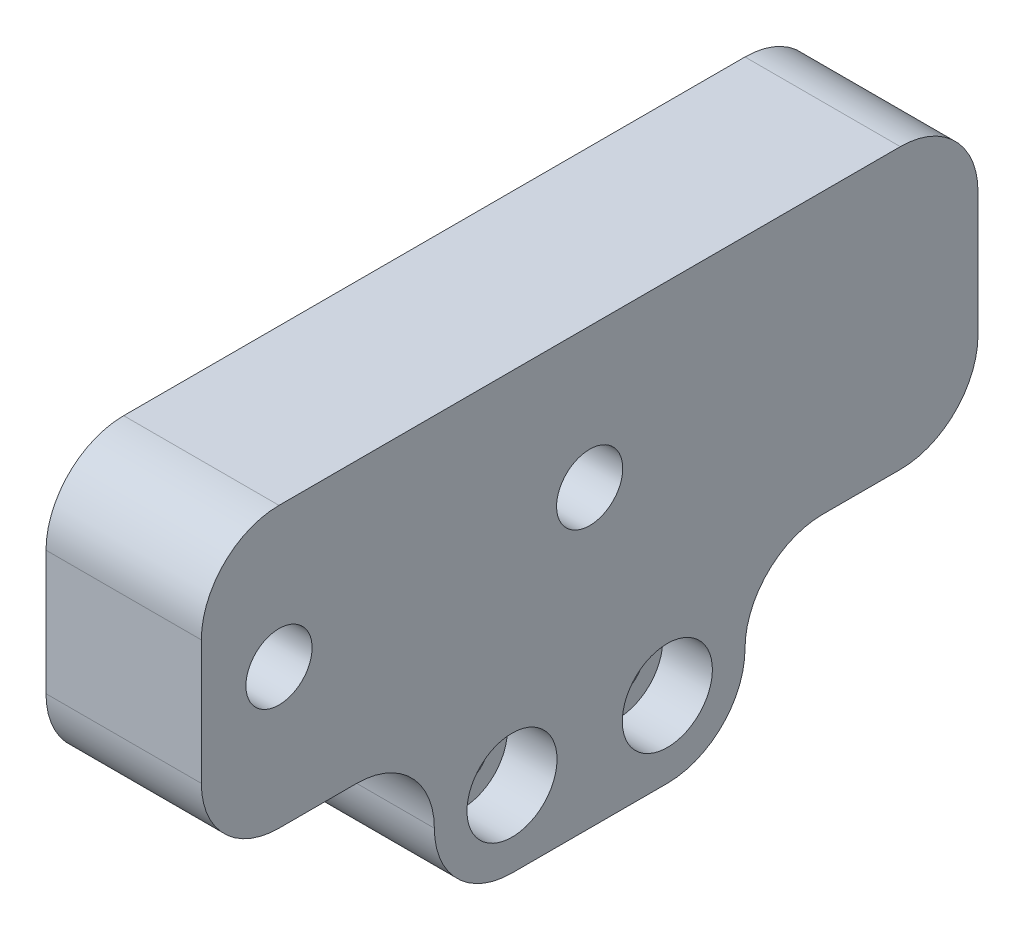
SolidWorks part; units mm, degrees
ref_plane "Front Plane" through (0, 0, 0) normal (0, 0, 1) x (1, 0, 0)
ref_plane "Top Plane" through (0, 0, 0) normal (0, 1, 0) x (1, 0, 0)
ref_plane "Right Plane" through (0, 0, 0) normal (1, 0, 0) x (0, 0, -1)
sketch "Profile" plane through (0, 0, 0) normal (0, 0, 1) x (1, 0, 0)
  line L1 (-6.35, 22.86) -> (6.35, 22.86)
  line L2 (-6.35, 22.86) -> (-6.35, 0)
  line L3 (-6.35, 0) -> (6.35, 0)
  line L4 (6.35, 22.86) -> (6.35, 0)
  line L5 (0, 0) -> (6.35, 0)
  line L6 (0, 0) -> (0, -12.7)
  line L7 (0, -12.7) -> (6.35, -12.7)
  line L8 (6.35, 0) -> (6.35, -12.7)
  dimension "D1" = 22.86
  dimension "D2" = 12.7
  dimension "D3" = 6.35
  dimension "D4" = 12.7
extrude "Boss-Extrude1" add sketch "Profile" along normal mid plane 25.4 contours L4 L1 L2 L3 | L8 L3 L6 L7 region at (0, 11.43, 0) region at (3.175, -6.35, 0)
sketch "Sketch7" plane through (0, 0, 12.7) normal (0, 0, 1) x (1, 0, 0)
  line L0 (0, -12.7) -> (6.35, -12.7) construction
  line L1 (0, 0) -> (-19.05, 0)
  line L2 (0, 0) -> (0, -12.7)
  line L3 (0, -12.7) -> (-19.05, -12.7)
  line L4 (-19.05, 0) -> (-19.05, -12.7)
  line L5 (-6.35, 22.86) -> (-6.35, 0) construction
  dimension "D1" = 12.7
extrude "Boss-Extrude2" add sketch "Sketch7" against normal up to surface (25.4 mm away) up to face at (0, 3.3867, -12.7)
sketch "ScrewHole" plane through (-19.05, 0, 0) normal (-1, 0, 0) x (0, 0, 1)
  line L0 (-12.7, 0) -> (12.7, 0) construction
  line L1 (0, -1000) -> (0, 49000) construction
  circle A0 centre (6.35, -6.477) radius 2.159
  circle A1 centre (-6.35, -6.477) radius 2.159
  dimension "D1" = 4.318
  dimension "D2" = 6.477
  dimension "D3" = 6.35
extrude "Cut-Extrude1" cut sketch "ScrewHole" against normal through all both and the other way through all
sketch "Sketch3" plane through (6.35, 0, 0) normal (1, 0, 0) x (0, 0, -1)
  circle A0 centre (-6.35, -6.477) radius 2.159 construction
  circle A1 centre (-6.35, -6.477) radius 2.159
  circle A2 centre (-6.35, -6.477) radius 3.683
  circle A3 centre (6.35, -6.477) radius 3.683
  dimension "D1" = 7.366
  dimension "D2" = 7.366
extrude "Cut-Extrude2" cut sketch "Sketch3" against normal blind 4.064
sketch "Sketch11" plane through (0, 0, 0) normal (0, 0, 1) x (1, 0, 0)
  line L0 (-6.35, 0) -> (6.35, 0)
  line L6 (-19.05, 0) -> (-19.05, -12.7)
  line L7 (-19.05, -12.7) -> (6.35, -12.7)
  line L8 (6.35, -12.7) -> (6.35, 22.86)
  line L9 (6.35, 22.86) -> (-6.35, 22.86)
  line L10 (-6.35, 22.86) -> (-6.35, 0)
  line L11 (-6.35, 0) -> (-19.05, 0)
  line L12 (-19.05, 0) -> (-19.05, -12.7)
  line L13 (-19.05, -12.7) -> (6.35, -12.7)
  line L14 (6.35, -12.7) -> (6.35, 22.86)
  line L15 (6.35, 22.86) -> (-6.35, 22.86)
  line L16 (-6.35, 22.86) -> (-6.35, 0)
  line L17 (-6.35, 0) -> (-19.05, 0)
  dimension "D1" = 0
extrude "Boss-Extrude4" add sketch "Sketch11" along normal blind 31.75 and the other way blind 31.75 contours L15 L16 L0 L14 region at (0, 11.43, 0)
sketch "Sketch13" plane through (-6.35, 0, 0) normal (-1, 0, 0) x (0, 0, 1)
  line L0 (-26.67, 17.78) -> (-6.35, 17.78) construction
  line L1 (-26.67, 17.78) -> (-26.67, 5.08) construction
  line L2 (-26.67, 5.08) -> (-6.35, 5.08) construction
  line L3 (-6.35, 17.78) -> (-6.35, 5.08) construction
  line L6 (-31.75, 22.86) -> (-31.75, 0) construction
  line L8 (12.7, 0) -> (-12.7, 0) construction
  circle A0 centre (-26.67, 17.78) radius 1.143
  circle A1 centre (-6.35, 17.78) radius 1.143
  circle A2 centre (-6.35, 5.08) radius 1.143
  circle A3 centre (-26.67, 5.08) radius 1.143
  point P17 (-31.75, 11.43)
  point P18 (-26.67, 11.43)
  point P19 (-16.51, 5.08)
  point P22 (0, 0)
  dimension "D1" = 2.286
  dimension "D2" = 2.286
  dimension "D3" = 2.286
  dimension "D4" = 2.286
  dimension "D5" = 20.32
  dimension "D6" = 12.7
  dimension "D7" = 16.51
sketch "Sketch14" plane through (6.35, 0, 0) normal (1, 0, 0) x (0, 0, -1)
  line L0 (-25.4, 11.43) -> (0, 11.43) construction
  line L1 (-31.75, 0) -> (-31.75, 22.86) construction
  circle A0 centre (-25.4, 11.43) radius 2.7051
  circle A1 centre (0, 11.43) radius 2.7051
  point P9 (-31.75, 11.43)
  dimension "D2" = 5.4102
  dimension "D3" = 5.4102
  dimension "D1" = 25.4
extrude "Cut-Extrude3" cut sketch "Sketch14" against normal blind 8.89
extrude "Cut-Extrude4" cut sketch "Sketch13" against normal blind 8.89
fillet "Fillet1" radius 6.35 8 edges at (-6.35, -12.7, -12.7) (-6.35, -12.7, 12.7) (0, 0, 31.75) (0, 22.86, 31.75) (0, 22.86, -31.75) (0, 0, -31.75) (0, 0, -12.7) (0, 0, 12.7)
